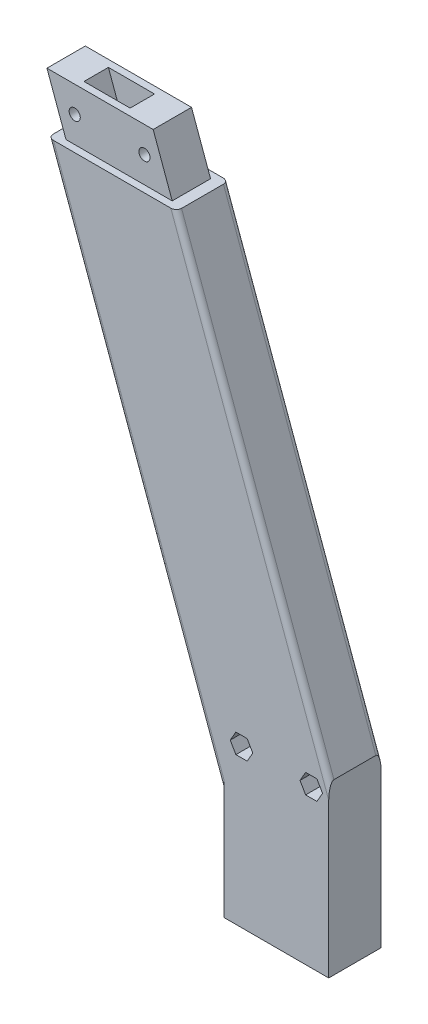
SolidWorks part; units mm, degrees
ref_plane "Front Plane" through (0, 0, 0) normal (0, 0, 1) x (1, 0, 0)
ref_plane "Top Plane" through (0, 0, 0) normal (0, 1, 0) x (1, 0, 0)
ref_plane "Right Plane" through (0, 0, 0) normal (1, 0, 0) x (0, 0, -1)
sketch "Sketch3" plane through (0, 0, 0) normal (0, 0, 1) x (1, 0, 0)
  line L1 (-127.0377, 609.9404) -> (92.9623, 609.9404)
  line L2 (-127.0377, 609.9404) -> (-127.0377, 389.9404)
  line L3 (-127.0377, 389.9404) -> (92.9623, 389.9404)
  line L4 (92.9623, 609.9404) -> (92.9623, 389.9404)
  dimension "D1" = 220
  dimension "D2" = 220
sketch "Sketch1" plane through (0, 0, 0) normal (0, 0, 1) x (1, 0, 0)
  line L0 (5, 40.95) -> (25, 40.95)
  line L1 (0, 0) -> (30, 0)
  line L2 (0, 0) -> (0, 34.5)
  line L3 (0, 34.5) -> (30, 34.5)
  line L4 (30, 0) -> (30, 34.5)
  line L5 (0, 0) -> (30, 0)
  line L6 (0, 0) -> (0, -4)
  line L7 (0, -4) -> (30, -4)
  line L8 (30, 0) -> (30, -4)
  line L9 (0, 34.5) -> (30, 34.5)
  line L10 (0, 34.5) -> (0, 44.5)
  line L11 (0, 44.5) -> (30, 44.5)
  line L12 (30, 34.5) -> (30, 44.5)
  line L14 (8.2332, 40.95) -> (6.6166, 43.75)
  line L15 (6.6166, 43.75) -> (3.3834, 43.75)
  line L16 (3.3834, 43.75) -> (1.7668, 40.95)
  line L17 (1.7668, 40.95) -> (3.3834, 38.15)
  line L18 (3.3834, 38.15) -> (6.6166, 38.15)
  line L19 (6.6166, 38.15) -> (8.2332, 40.95)
  line L20 (21.7668, 40.95) -> (23.3834, 38.15)
  line L21 (23.3834, 38.15) -> (26.6166, 38.15)
  line L22 (26.6166, 38.15) -> (28.2332, 40.95)
  line L23 (28.2332, 40.95) -> (26.6166, 43.75)
  line L24 (26.6166, 43.75) -> (23.3834, 43.75)
  line L25 (23.3834, 43.75) -> (21.7668, 40.95)
  circle A0 centre (15, 8) radius 6.5
  circle A1 centre (5, 40.95) radius 1.55
  circle A2 centre (25, 40.95) radius 1.55
  circle A3 centre (5, 40.95) radius 2.8 construction
  circle A4 centre (25, 40.95) radius 2.8 construction
  point P10 (15, 0)
  point P16 (5, 42.5)
  point P17 (5, 39.4)
  point P18 (15, 40.95)
  point P19 (15, 34.5)
  dimension "D4" = 13
  dimension "D7" = 3.1
  dimension "D10" = 5.6
  dimension "D1" = 30
  dimension "D2" = 34.5
  dimension "D3" = 4
  dimension "D5" = 8
  dimension "D6" = 20
  dimension "D8" = 4.9
  dimension "D9" = 2
sketch "Sketch2" plane through (0, 0, 0) normal (0, 0, 1) x (1, 0, 0)
  line L0 (0, 34.5) -> (-53.8676, 182.5)
  line L1 (-53.8676, 182.5) -> (-53.8676, 34.5)
  line L2 (-53.8676, 34.5) -> (0, 34.5)
  line L3 (30, 44.5) -> (-82.8834, 354.6447)
  line L4 (-82.8834, 354.6447) -> (-119.7157, 354.6447)
  line L5 (-119.7157, 354.6447) -> (-3.1925, 34.5)
  line L6 (-53.8676, 182.5) -> (-115.4312, 351.6447)
  line L7 (-55.9682, 179.5) -> (-19.136, 179.5)
  line L8 (-50.5087, 164.5) -> (-13.6764, 164.5)
  line L9 (-44.8223, 172) -> (-24.8223, 172)
  line L10 (-24.8223, 168.7668) -> (-22.0223, 170.3834)
  line L11 (-22.0223, 170.3834) -> (-22.0223, 173.6166)
  line L12 (-22.0223, 173.6166) -> (-24.8223, 175.2332)
  line L13 (-24.8223, 175.2332) -> (-27.6223, 173.6166)
  line L14 (-27.6223, 173.6166) -> (-27.6223, 170.3834)
  line L15 (-27.6223, 170.3834) -> (-24.8223, 168.7668)
  line L16 (-44.8223, 168.7668) -> (-42.0223, 170.3834)
  line L17 (-42.0223, 170.3834) -> (-42.0223, 173.6166)
  line L18 (-42.0223, 173.6166) -> (-44.8223, 175.2332)
  line L19 (-44.8223, 175.2332) -> (-47.6223, 173.6166)
  line L20 (-47.6223, 173.6166) -> (-47.6223, 170.3834)
  line L21 (-47.6223, 170.3834) -> (-44.8223, 168.7668)
  line L22 (-37.5521, 179.5) -> (-32.0925, 164.5)
  line L23 (-22.3285, 179.5) -> (-16.869, 164.5)
  line L24 (-52.7757, 179.5) -> (-47.3161, 164.5)
  line L25 (-44.1637, 179.5) -> (4.9723, 44.5)
  line L26 (0, 44.5) -> (30, 44.5) construction
  line L27 (-30.9405, 179.5) -> (18.1955, 44.5)
  line L28 (4.9723, 44.5) -> (18.1955, 44.5)
  line L29 (-44.1637, 179.5) -> (-30.9405, 179.5)
  line L30 (18.1955, 44.5) -> (30, 44.5)
  line L31 (4.9723, 44.5) -> (0, 44.5)
  line L32 (0, 44.5) -> (0, 34.5)
  line L33 (-3.1925, 34.5) -> (0, 25.7286)
  line L34 (0, 0) -> (0, 34.5) construction
  line L35 (0, 25.7286) -> (0, 34.5)
  circle A0 centre (-53.8676, 182.5) radius 2.5
  circle A1 centre (-66.1803, 216.3289) radius 2.5
  circle A2 centre (-78.493, 250.1579) radius 2.5
  circle A3 centre (-90.8058, 283.9868) radius 2.5
  circle A4 centre (-103.1185, 317.8157) radius 2.5
  circle A5 centre (-115.4312, 351.6447) radius 2.5
  circle A6 centre (-115.4312, 351.6447) radius 3
  circle A7 centre (-53.8676, 182.5) radius 3
  circle A8 centre (-24.8223, 172) radius 2.8 construction
  circle A9 centre (-44.8223, 172) radius 2.8 construction
  circle A10 centre (-44.8223, 172) radius 1.6
  circle A11 centre (-24.8223, 172) radius 1.6
  point P44 (-34.8223, 172)
  point P45 (-34.8223, 172)
  dimension "D3" = 5
  dimension "D5" = 6
  dimension "D8" = 5.6
  dimension "D10" = 3.2
  dimension "D1" = 148
  dimension "D2" = 70
  dimension "D6" = 180
  dimension "D7" = 15
  dimension "D9" = 20
  dimension "D11" = 3
  dimension "D12" = 3
  dimension "D13" = 12.4258
  dimension "D4" = 6
extrude "Boss-Extrude1" add sketch "Sketch1" along normal blind 15 contours L1 L4 L3 L2 A0 | L3 L12 L11 L10 L25 L24 L23 L22 L21 L20 L19 L18 L17 L16 L15 L14 | A0 | L8 L1 L6 L7 | A1 L14 L15 L16 L17 L18 L19 | A2 L20 L21 L22 L23 L24 L25 region at (7.3508, 39.5928, 0) region at (22.6492, 42.3072, 0) region at (15, 18.6108, 0) region at (15, -2, 0) region at (15, 39.1794, 0) region at (15, 8, 0)
extrude "Cut-Extrude2" cut sketch "Sketch1<3>" along normal blind 2 contours A0 region at (15, 8, 0)
sketch "Sketch1<3>" plane through (0, 0, 0) normal (0, 0, 1) x (1, 0, 0) same geometry as "Sketch1"
sketch "Sketch4" plane through (0, 0, 15) normal (0, 0, 1) x (1, 0, 0)
  line L1 (8.2332, 40.95) -> (6.6166, 43.75)
  line L2 (6.6166, 43.75) -> (3.3834, 43.75)
  line L3 (3.3834, 43.75) -> (1.7668, 40.95)
  line L4 (1.7668, 40.95) -> (3.3834, 38.15)
  line L5 (3.3834, 38.15) -> (6.6166, 38.15)
  line L6 (6.6166, 38.15) -> (8.2332, 40.95)
  line L7 (28.2332, 40.95) -> (26.6166, 43.75)
  line L8 (26.6166, 43.75) -> (23.3834, 43.75)
  line L9 (23.3834, 43.75) -> (21.7668, 40.95)
  line L10 (21.7668, 40.95) -> (23.3834, 38.15)
  line L11 (23.3834, 38.15) -> (26.6166, 38.15)
  line L12 (26.6166, 38.15) -> (28.2332, 40.95)
  circle A0 centre (5, 40.95) radius 2.8 construction
  circle A1 centre (25, 40.95) radius 2.8 construction
extrude "Cut-Extrude3" cut sketch "Sketch4" against normal blind 4.5
extrude "Boss-Extrude2" add sketch "Sketch2" along normal blind 15 contours L27 L30 L3 L8 | L25 L28 L27 L8 | L32 L31 L25 L8 L0 | L8 L5 L2 L0 | L33 L35 L2 region at (-25.2543, 99.5, 0) region at (-1.0642, 31.5762, 0) region at (-20.8265, 103.404, 0) region at (-10.2543, 104.5, 0) region at (2.2595, 104.5, 0)
extrude "Cut-Extrude4" cut sketch "Sketch2<3>" along normal offset from surface (11 mm away) 4 contours L25 L28 L27 L8 | L9 L25 L8 L22 | L7 L25 L9 L22 | L27 L7 L22 L9 | L27 L9 L22 L8 region at (-36.7632, 168.25, 0) region at (-10.2543, 104.5, 0) region at (-39.493, 175.75, 0) region at (-30.1516, 168.25, 0) region at (-32.8814, 175.75, 0) up to face at (-0.6975, 65.2048, 15)
sketch "Sketch2<3>" plane through (0, 0, 0) normal (0, 0, 1) x (1, 0, 0) same geometry as "Sketch2"
extrude "Boss-Extrude4" add sketch "Sketch2<5>" along normal offset from surface (13 mm away) 2 contours L25 L7 L0 L8 L9 L17 L16 L21 L20 L19 L18 | A10 L17 L18 L19 L20 L21 L16 | L25 L17 L9 | L9 L25 L8 L22 | L7 L25 L9 L22 | L27 L7 L22 L9 | L27 L9 L22 L8 | L7 L27 L9 L14 L13 L12 L11 L10 L15 L8 L23 | A11 L14 L15 L10 L11 L12 L13 | L9 L27 L14 region at (-49.8526, 172.0703, 0) region at (-36.7632, 168.25, 0) region at (-39.493, 175.75, 0) region at (-30.1516, 168.25, 0) region at (-41.8262, 172.5389, 0) region at (-32.8814, 175.75, 0) region at (-42.1079, 172.8083, 0) region at (-26.3584, 167.5121, 0) region at (-27.8185, 171.4611, 0) region at (-27.5368, 171.1917, 0) up to face at (-0.6975, 65.2048, 15)
sketch "Sketch2<5>" plane through (0, 0, 0) normal (0, 0, 1) x (1, 0, 0) same geometry as "Sketch2"
extrude "Cut-Extrude5" cut sketch "Sketch2<6>" along normal blind 2 contours L7 L27 L9 L14 L13 L12 L11 L10 L15 L8 L23 | L27 L9 L22 L8 | L9 L25 L8 L22 | L7 L25 L9 L22 | L27 L7 L22 L9 | L25 L7 L0 L8 L9 L17 L16 L21 L20 L19 L18 | A10 L17 L18 L19 L20 L21 L16 | L25 L17 L9 | A11 L14 L15 L10 L11 L12 L13 | L9 L27 L14 region at (-49.8526, 172.0703, 0) region at (-36.7632, 168.25, 0) region at (-39.493, 175.75, 0) region at (-30.1516, 168.25, 0) region at (-41.8262, 172.5389, 0) region at (-32.8814, 175.75, 0) region at (-42.1079, 172.8083, 0) region at (-26.3584, 167.5121, 0) region at (-27.8185, 171.4611, 0) region at (-27.5368, 171.1917, 0)
sketch "Sketch2<6>" plane through (0, 0, 0) normal (0, 0, 1) x (1, 0, 0) same geometry as "Sketch2"
extrude "Cut-Extrude6" cut sketch "Sketch2<7>" along normal offset from surface (11 mm away) 2 contours L7 L25 L9 L22 | L9 L25 L8 L22 | L27 L9 L22 L8 | L27 L7 L22 L9 region at (-36.7632, 168.25, 0) region at (-39.493, 175.75, 0) region at (-30.1516, 168.25, 0) region at (-32.8814, 175.75, 0) up to face at (-43.2223, 172, 13)
sketch "Sketch2<7>" plane through (0, 0, 0) normal (0, 0, 1) x (1, 0, 0) same geometry as "Sketch2"
extrude "Boss-Extrude8" add sketch "Sketch2<9>" along normal blind 4 contours L25 L28 L27 L8 region at (-10.2543, 104.5, 0)
sketch "Sketch2<9>" plane through (0, 0, 0) normal (0, 0, 1) x (1, 0, 0) same geometry as "Sketch2"
extrude "Boss-Extrude10" add sketch "Sketch2<11>" along normal offset from surface (4 mm away) 2 contours L9 L25 L8 L22 | L7 L25 L9 L22 | L27 L9 L22 L8 | L27 L7 L22 L9 region at (-36.7632, 168.25, 0) region at (-39.493, 175.75, 0) region at (-30.1516, 168.25, 0) region at (-32.8814, 175.75, 0) up to face at (-23.9047, 172, 2) offset beyond the face yes
sketch "Sketch2<11>" plane through (0, 0, 0) normal (0, 0, 1) x (1, 0, 0) same geometry as "Sketch2"
extrude "Cut-Extrude8" cut sketch "Sketch2<12>" along normal blind 2 contours L7 L25 L9 L22 | L9 L25 L8 L22 | L27 L9 L22 L8 | L27 L7 L22 L9 region at (-36.7632, 168.25, 0) region at (-39.493, 175.75, 0) region at (-30.1516, 168.25, 0) region at (-32.8814, 175.75, 0)
sketch "Sketch2<12>" plane through (0, 0, 0) normal (0, 0, 1) x (1, 0, 0) same geometry as "Sketch2"
sketch "Sketch6" plane through (0, 0, 0) normal (0, 0, -1) x (-1, 0, 0)
  line L0 (-18.1955, 44.5) -> (-4.9723, 44.5)
  line L1 (-4.9723, 44.5) -> (0.4873, 59.5)
  line L2 (44.1637, 179.5) -> (-4.9723, 44.5) construction
  line L3 (0.4873, 59.5) -> (-12.7359, 59.5)
  line L4 (30.9405, 179.5) -> (-18.1955, 44.5) construction
  line L5 (-12.7359, 59.5) -> (-18.1955, 44.5)
  dimension "D1" = 15
extrude "Cut-Extrude9" cut sketch "Sketch6" against normal up to next
fillet "Fillet1" radius 1.5 4 edges at (-25.2543, 95.1143, 0) (-25.2543, 95.1143, 15) (8.1618, 104.5, 0) (8.1618, 104.5, 15)
